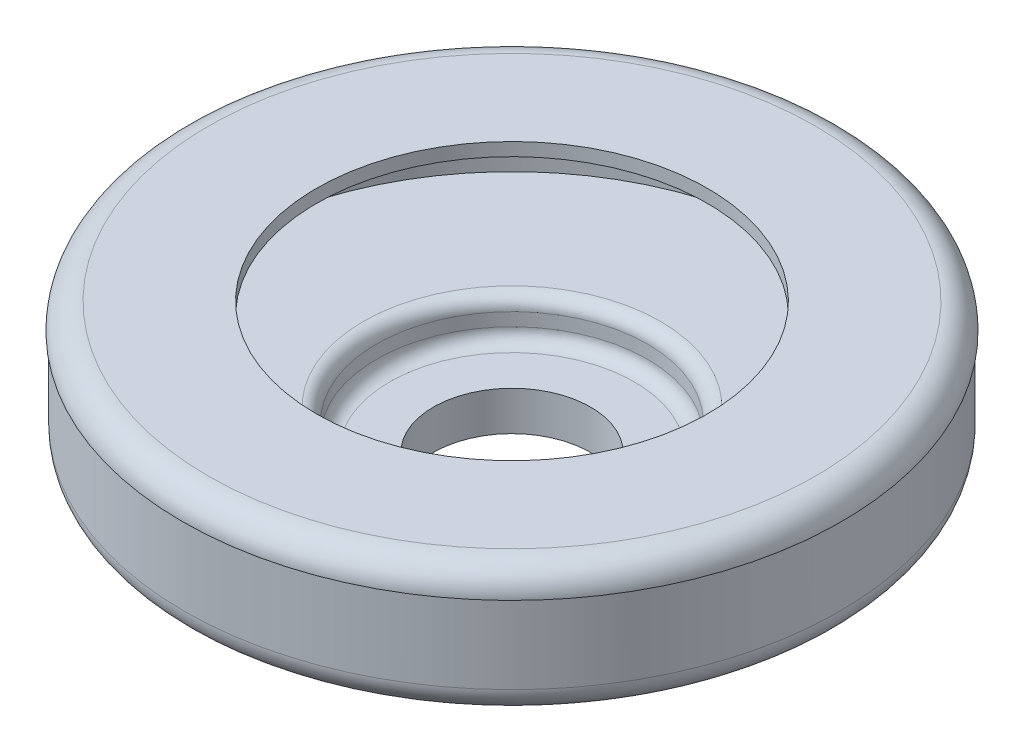
SolidWorks part; units mm, degrees
material "AISI 304"
ref_plane "Спереди" through (0, 0, 0) normal (0, 0, 1) x (1, 0, 0)
ref_plane "Сверху" through (0, 0, 0) normal (0, 1, 0) x (1, 0, 0)
ref_plane "Справа" through (0, 0, 0) normal (1, 0, 0) x (0, 0, -1)
sketch "Эскиз2" plane through (0, 0, 0) normal (0, 1, 0) x (1, 0, 0)
  line L0 (38.7085, 29.0314) -> (41.2915, 30.9686) construction
  line L1 (-50, -42.5) -> (50, -42.5)
  line L2 (-50, -42.5) -> (-50, 42.5)
  line L3 (-50, 42.5) -> (50, 42.5)
  line L4 (50, -42.5) -> (50, 42.5)
  line L5 (-50, -42.5) -> (50, 42.5) construction
  line L6 (-50, 42.5) -> (50, -42.5) construction
  line L7 (-40, -30) -> (40, -30) construction
  line L8 (-40, -30) -> (-40, 30) construction
  line L9 (-40, 30) -> (40, 30) construction
  line L10 (40, -30) -> (40, 30) construction
  line L11 (-40, -30) -> (40, 30) construction
  line L12 (-40, 30) -> (40, -30) construction
  line L13 (-50, 0) -> (50, 0) construction
  line L14 (35.7977, 32.9124) -> (38.3808, 34.8496)
  line L15 (41.6192, 25.1504) -> (44.2023, 27.0876)
  line L16 (0, 42.5) -> (0, -42.5) construction
  line L17 (-41.2, 30.9) -> (-38.8, 29.1) construction
  line L18 (-41.2, -30.9) -> (-38.8, -29.1) construction
  line L19 (-38.5, 34.5) -> (-36.1, 32.7)
  line L20 (-43.9, 27.3) -> (-41.5, 25.5)
  line L21 (38.5, -34.5) -> (36.1, -32.7)
  line L22 (-43.9, -27.3) -> (-41.5, -25.5)
  line L23 (-38.5, -34.5) -> (-36.1, -32.7)
  line L24 (41.2, -30.9) -> (38.8, -29.1) construction
  line L25 (43.9, -27.3) -> (41.5, -25.5)
  arc A0 (35.7977, 32.9124) -> (41.6192, 25.1504) centre (38.7085, 29.0314) ccw
  arc A1 (44.2023, 27.0876) -> (38.3808, 34.8496) centre (41.2915, 30.9686) ccw
  arc A2 (-38.5, 34.5) -> (-43.9, 27.3) centre (-41.2, 30.9) ccw
  arc A3 (-41.5, 25.5) -> (-36.1, 32.7) centre (-38.8, 29.1) ccw
  arc A4 (-43.9, -27.3) -> (-38.5, -34.5) centre (-41.2, -30.9) ccw
  arc A5 (-36.1, -32.7) -> (-41.5, -25.5) centre (-38.8, -29.1) ccw
  arc A6 (38.5, -34.5) -> (43.9, -27.3) centre (41.2, -30.9) ccw
  arc A7 (41.5, -25.5) -> (36.1, -32.7) centre (38.8, -29.1) ccw
  circle A8 centre (0, 0) radius 6
  point P0 (0, 0)
  point P5 (0, 0)
  point P15 (40, 30)
  point P26 (-40, 30)
  point P32 (40, -30)
  point P33 (-40, -30)
  dimension "D1" = 80
  dimension "D2" = 60
  dimension "D3" = 100
  dimension "D4" = 85
extrude "Бобышка-Вытянуть1" add sketch "Эскиз2" along normal blind 2
sketch "Эскиз3" plane through (0, 2, 0) normal (0, 1, 0) x (1, 0, 0)
  circle A0 centre (0, 0) radius 25
extrude "Бобышка-Вытянуть2" add sketch "Эскиз3" against normal blind 10
shell "Оболочка1" thickness 3 removed face at (-40, 2, 30)
sketch "Эскиз4" plane through (0, -5, 0) normal (0, 1, 0) x (1, 0, 0)
  circle A0 centre (0, 0) radius 6
sketch "Эскиз5" plane through (0, -5, 0) normal (0, 1, 0) x (1, 0, 0)
  circle A0 centre (0, 0) radius 13.3323
extrude "Бобышка-Вытянуть3" add sketch "Эскиз5" against normal blind 6
shell "Оболочка2" thickness 3 removed face at (0, -5, 22)
fillet "Скругление2" radius 1 4 edges at (0, -11, 13.3323) (0, -8, 13.3323) (0, -8, 10.3323) (0, -5, 10.3323)
extrude "Вырез-Вытянуть2" cut sketch "Эскиз4" against normal mid plane 39.8 contours A0
fillet "Скругление3" radius 1 4 edges at (50, 1, 42.5) (50, 1, -42.5) (-50, 1, -42.5) (-50, 1, 42.5)
fillet "Скругление4" radius 0.25 16 edges at (-49.7071, 0, 42.2071) (-50, 0, 0) (-49.7071, 0, -42.2071) (0, 0, -42.5) (49.7071, 0, -42.2071) (50, 0, 0) (49.7071, 0, 42.2071) (-49.7071, 2, 42.2071) (-50, 2, 0) (-49.7071, 2, -42.2071) (0, 2, -42.5) (49.7071, 2, -42.2071) (50, 2, 0) (49.7071, 2, 42.2071) (0, 0, 42.5) (0, 2, 42.5)
sketch "Эскиз6" plane through (0, 2, 0) normal (0, 1, 0) x (1, 0, 0)
  line L1 (-61.7019, -53.2469) -> (61.7019, -53.2469)
  line L2 (-61.7019, -53.2469) -> (-61.7019, 53.2469)
  line L3 (-61.7019, 53.2469) -> (61.7019, 53.2469)
  line L4 (61.7019, -53.2469) -> (61.7019, 53.2469)
  line L5 (-61.7019, -53.2469) -> (61.7019, 53.2469) construction
  line L6 (-61.7019, 53.2469) -> (61.7019, -53.2469) construction
  circle A0 centre (0, 0) radius 25.1479
extrude "Вырез-Вытянуть3" cut sketch "Эскиз6" against normal blind 3
sketch "Эскиз7" plane through (0, 2, 0) normal (0, 1, 0) x (1, 0, 0)
  circle A0 centre (0, 0) radius 22 construction
  circle A1 centre (0, 0) radius 22
  circle A2 centre (0, 0) radius 14.9171
extrude "Бобышка-Вытянуть4" add sketch "Эскиз7" against normal blind 1
fillet "Скругление5" radius 2 2 edges at (0, 2, 25.1479) (0, -8, 25)
